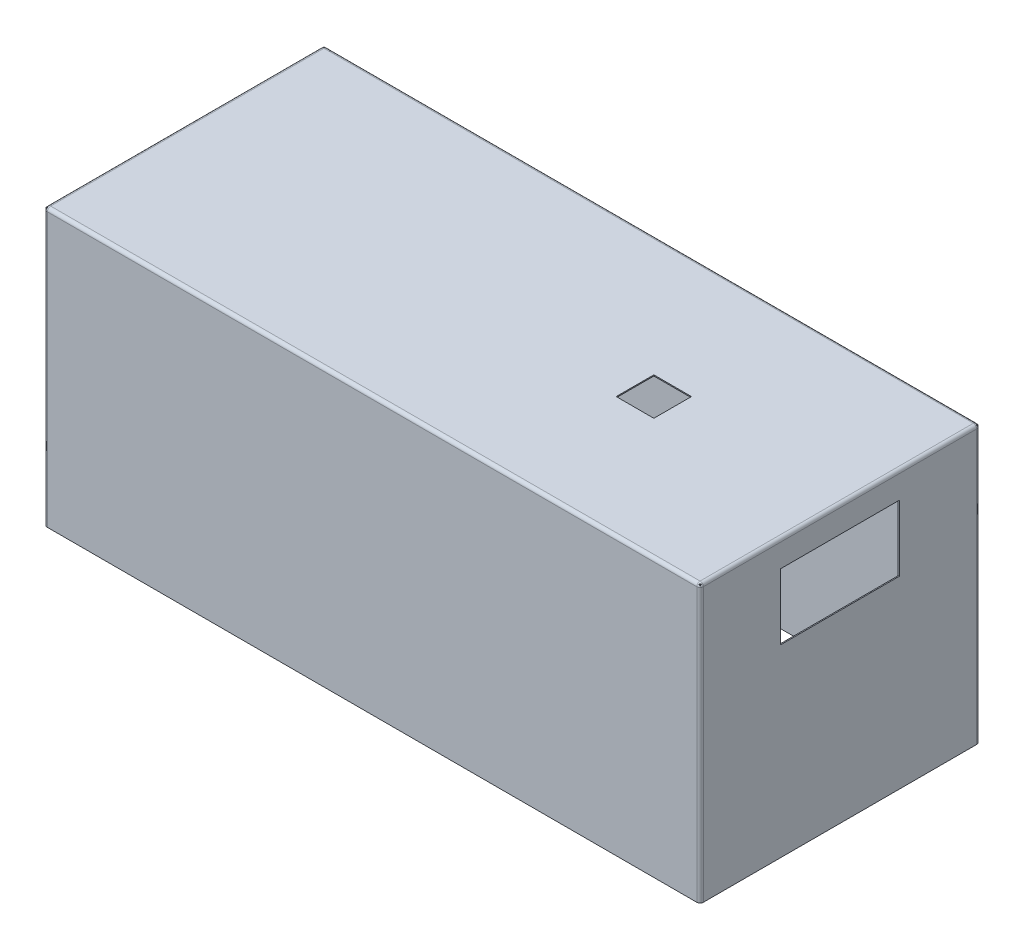
SolidWorks part; units mm, degrees
material "Alumina"
ref_plane "Front Plane" through (0, 0, 0) normal (0, 0, 1) x (1, 0, 0)
ref_plane "Top Plane" through (0, 0, 0) normal (0, 1, 0) x (1, 0, 0)
ref_plane "Right Plane" through (0, 0, 0) normal (1, 0, 0) x (0, 0, -1)
sketch "Sketch2" plane through (0, 0, 0) normal (0, 1, 0) x (1, 0, 0)
  line L1 (-498.1, 212.5) -> (498.1, 212.5)
  line L2 (-498.1, 212.5) -> (-498.1, -212.5)
  line L3 (-498.1, -212.5) -> (498.1, -212.5)
  line L4 (498.1, 212.5) -> (498.1, -212.5)
  line L5 (-498.1, 212.5) -> (498.1, -212.5) construction
  line L6 (-498.1, -212.5) -> (498.1, 212.5) construction
  line L7 (-496.5125, 210.9125) -> (496.5125, 210.9125)
  line L8 (-496.5125, 210.9125) -> (-496.5125, -210.9125)
  line L9 (-496.5125, -210.9125) -> (496.5125, -210.9125)
  line L10 (496.5125, 210.9125) -> (496.5125, -210.9125)
  line L11 (-496.5125, 210.9125) -> (496.5125, -210.9125) construction
  line L12 (-496.5125, -210.9125) -> (496.5125, 210.9125) construction
  point P0 (0, 0)
  point P6 (0, 0)
  dimension "D1" = 996.2
  dimension "D2" = 425
  dimension "D3" = 993.025
  dimension "D4" = 421.825
extrude "Boss-Extrude1" add sketch "Sketch2" along normal blind 420
sketch "Sketch3" plane through (0, 0, 0) normal (0, 1, 0) x (1, 0, 0)
  line L1 (-498.1, 212.5) -> (498.1, 212.5)
  line L2 (-498.1, 212.5) -> (-498.1, -212.5)
  line L3 (-498.1, -212.5) -> (498.1, -212.5)
  line L4 (498.1, 212.5) -> (498.1, -212.5)
  line L5 (-498.1, 212.5) -> (498.1, -212.5) construction
  line L6 (-498.1, -212.5) -> (498.1, 212.5) construction
  point P0 (0, 0)
  dimension "D1" = 996.2
  dimension "D2" = 425
extrude "Boss-Extrude2" add sketch "Sketch3" against normal blind 1.5875 from offset 420
fillet "Fillet2" radius 5 8 edges at (0, 420, 212.5) (-498.1, 420, 0) (0, 420, -212.5) (498.1, 420, 0) (498.1, 210, 212.5) (-498.1, 210, 212.5) (-498.1, 210, -212.5) (498.1, 210, -212.5)
sketch "Sketch4" plane through (-498.1, 0, 0) normal (-1, 0, 0) x (0, 0, 1)
  line L0 (-207.5, 0) -> (207.5, 0) construction
  line L1 (-40, 0) -> (40, 0)
  line L2 (-40, 0) -> (-40, 80)
  line L3 (-40, 80) -> (40, 80)
  line L4 (40, 0) -> (40, 80)
  line L5 (-40, 0) -> (40, 80) construction
  line L6 (-40, 80) -> (40, 0) construction
  point P4 (0, 40)
  dimension "D1" = 80
  dimension "D2" = 80
extrude "Cut-Extrude1" cut sketch "Sketch4" against normal up to next
sketch "Sketch5" plane through (0, 0, 212.5) normal (0, 0, 1) x (1, 0, 0)
  line L0 (102.4542, 1871.2645) -> (102.4542, 2121.2645) construction
  dimension "D1" = 250
sketch "Sketch6" plane through (0, 0, -212.5) normal (0, 0, -1) x (-1, 0, 0)
  line L0 (-163.7052, 31.2035) -> (-163.7052, 281.2035) construction
  dimension "D1" = 250
sketch "Sketch7" plane through (0, 0, 0) normal (0, 1, 0) x (1, 0, 0)
  line L0 (-231, 0) -> (231, 0) construction
  line L1 (186.825, 28.575) -> (243.975, 28.575)
  line L2 (186.825, 28.575) -> (186.825, -28.575)
  line L3 (186.825, -28.575) -> (243.975, -28.575)
  line L4 (243.975, 28.575) -> (243.975, -28.575)
  line L5 (186.825, 28.575) -> (243.975, -28.575) construction
  line L6 (186.825, -28.575) -> (243.975, 28.575) construction
  point P0 (215.4, 0)
  dimension "D1" = 57.15
  dimension "D2" = 215.4
extrude "Cut-Extrude2" cut sketch "Sketch7" along normal up to surface (420 mm away) up to face at (0, 420, 0)
sketch "Sketch8" plane through (0, 0, 0) normal (1, 0, 0) x (0, 0, -1)
  line L0 (0, 231) -> (0, -231) construction
  line L1 (-90, 380) -> (90, 380)
  line L2 (-90, 380) -> (-90, 280)
  line L3 (-90, 280) -> (90, 280)
  line L4 (90, 380) -> (90, 280)
  line L5 (-90, 380) -> (90, 280) construction
  line L6 (-90, 280) -> (90, 380) construction
  line L7 (233.75, 0) -> (-233.75, 0) construction
  point P0 (0, 330)
  dimension "D1" = 330
  dimension "D2" = 180
  dimension "D3" = 100
extrude "Cut-Extrude3" cut sketch "Sketch8" along normal up to surface (498.1 mm away) up to face at (498.1, 207.5, 0)
sketch "Sketch9" plane through (0, 0, 0) normal (1, 0, 0) x (0, 0, -1)
  line L0 (0, 231) -> (0, -231) construction
  line L1 (90, 180) -> (-90, 180)
  line L2 (90, 180) -> (90, 80)
  line L3 (90, 80) -> (-90, 80)
  line L4 (-90, 180) -> (-90, 80)
  line L5 (90, 180) -> (-90, 80) construction
  line L6 (90, 80) -> (-90, 180) construction
  line L7 (233.75, 0) -> (-233.75, 0) construction
  point P0 (0, 130)
  dimension "D1" = 180
  dimension "D2" = 100
  dimension "D3" = 130
extrude "Cut-Extrude4" cut sketch "Sketch9" against normal up to surface (498.1 mm away) up to face at (-498.1, 123.75, 0)
equation "\"sheetMetalThickness\"= 1in / 16"
equation "\"shellLength\"= 920mm + 3in"
equation "\"shellWidth\"= 425mm"
equation "\"shellHeight\"= 420mm"
equation "\"D1@Sketch2\"=\"shellLength\""
equation "\"D2@Sketch2\"=\"shellWidth\""
equation "\"D3@Sketch2\"=\"shellLength\"-\"sheetMetalThickness\"*2"
equation "\"D4@Sketch2\"=\"shellWidth\"-\"sheetMetalThickness\"*2"
equation "\"D1@Boss-Extrude1\"=\"shellHeight\""
equation "\"D1@Sketch3\"=\"shellLength\""
equation "\"D2@Sketch3\"=\"shellWidth\""
equation "\"D19@Boss-Extrude2\"=\"shellHeight\""
equation "\"D1@Boss-Extrude2\"=\"sheetMetalThickness\""
equation "\"D2@Sketch7\"=\"shellLength\"/2 -282.7"
equation "\"D1@Sketch8\"=\"shellHeight\"-90"
